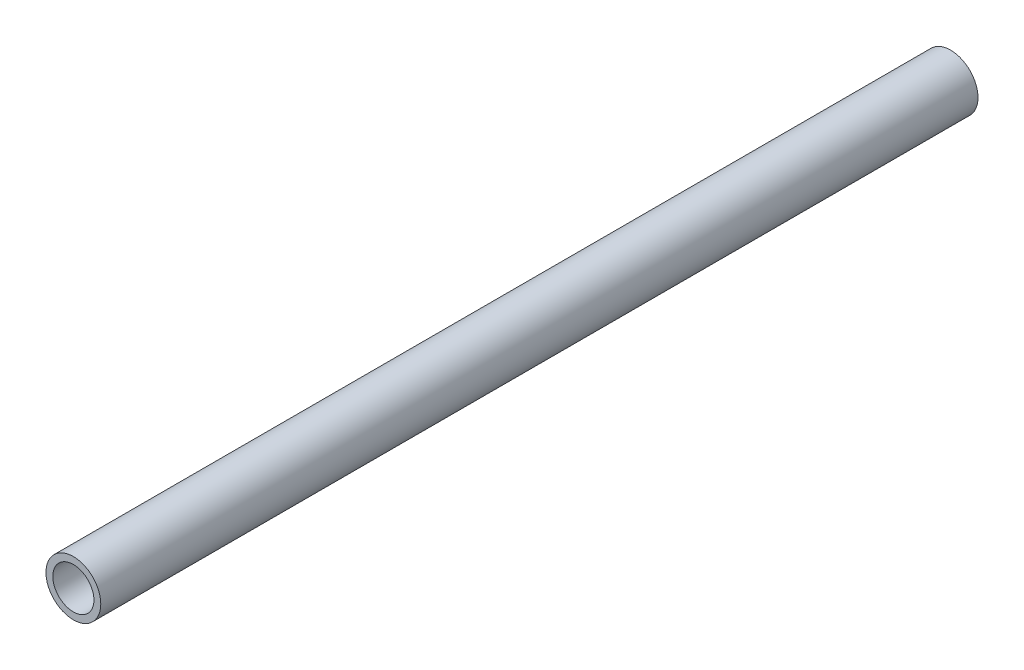
SolidWorks part; units mm, degrees
material "Pine"
ref_plane "Front Plane" through (0, 0, 0) normal (0, 0, 1) x (1, 0, 0)
ref_plane "Top Plane" through (0, 0, 0) normal (0, 1, 0) x (1, 0, 0)
ref_plane "Right Plane" through (0, 0, 0) normal (1, 0, 0) x (0, 0, -1)
sketch "Sketch1" plane through (0, 0, 0) normal (0, 0, 1) x (1, 0, 0)
  circle A0 centre (0, 0) radius 6.35
  circle A1 centre (0, 0) radius 4.7625
  dimension "D1" = 12.7
  dimension "D2" = 9.525
extrude "Boss-Extrude1" add sketch "Sketch1" along normal mid plane 203.2
equation "\"D2@Sketch1\"=0.50 - (1/8)"
